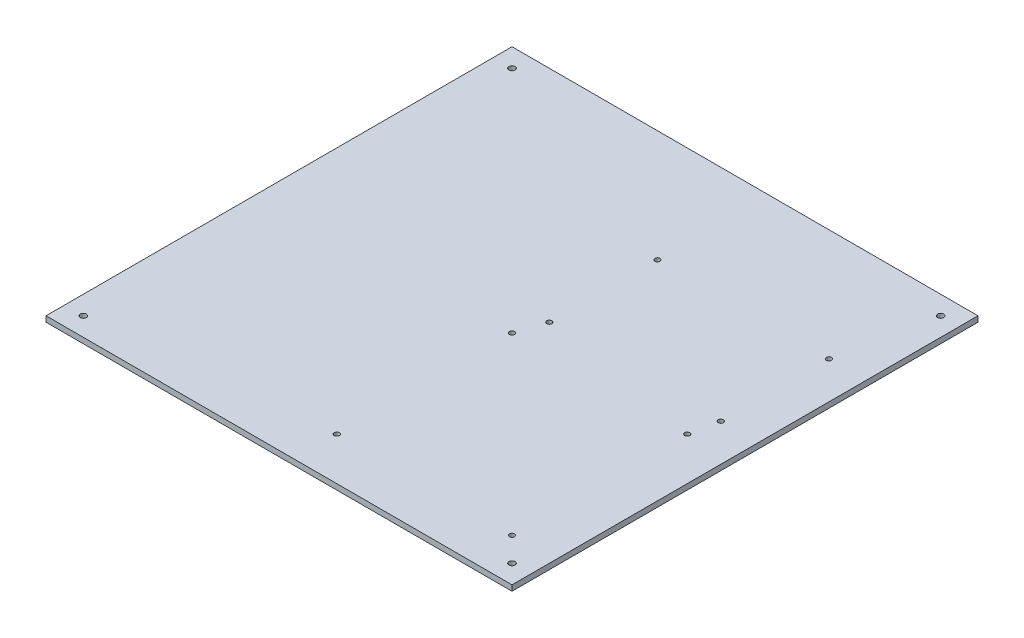
SolidWorks part; units mm, degrees
ref_plane "Front Plane" through (0, 0, 0) normal (0, 0, 1) x (1, 0, 0)
ref_plane "Top Plane" through (0, 0, 0) normal (0, 1, 0) x (1, 0, 0)
ref_plane "Right Plane" through (0, 0, 0) normal (1, 0, 0) x (0, 0, -1)
sketch "Sketch1" plane through (0, 0, 0) normal (0, 1, 0) x (1, 0, 0)
  line L0 (0, 0) -> (0, -250) construction
  line L1 (-125, 0) -> (125, 0)
  line L2 (-125, 0) -> (-125, -250)
  line L3 (-125, -250) -> (125, -250)
  line L4 (125, 0) -> (125, -250)
  line L5 (0, -1.65) -> (0, 1.65) construction
  line L6 (-125, -125) -> (125, -125) construction
  line L7 (55, -130) -> (55, -230) construction
  line L8 (-105, -161.34) -> (-31.34, -161.34) construction
  line L9 (-105, -15) -> (-31.34, -15) construction
  line L10 (-105, -15) -> (-105, -88.66) construction
  line L11 (-105, -88.66) -> (-31.34, -88.66) construction
  line L12 (-31.34, -15) -> (-31.34, -88.66) construction
  line L13 (-105, -161.34) -> (-105, -235) construction
  line L14 (-105, -235) -> (-31.34, -235) construction
  line L15 (-31.34, -161.34) -> (-31.34, -235) construction
  line L16 (-105, -88.66) -> (-105, -161.34) construction
  line L17 (5, -130) -> (105, -130) construction
  line L18 (5, -130) -> (5, -230) construction
  line L19 (5, -230) -> (105, -230) construction
  line L20 (105, -130) -> (105, -230) construction
  line L21 (5, -180) -> (105, -180) construction
  line L22 (-60.805, -122.8687) -> (-38.005, -122.8687) construction
  line L23 (9, -43) -> (109, -43) construction
  line L24 (9, -43) -> (9, -122) construction
  line L25 (9, -122) -> (109, -122) construction
  line L26 (109, -43) -> (109, -122) construction
  line L27 (-102.037, -122.1462) -> (-79.237, -122.1462) construction
  line L28 (-102.037, -122.1462) -> (-102.037, -145.0462) construction
  line L29 (-102.037, -145.0462) -> (-79.237, -145.0462) construction
  line L30 (-79.237, -122.1462) -> (-79.237, -145.0462) construction
  line L35 (-60.805, -122.8687) -> (-60.805, -145.7687) construction
  line L36 (-60.805, -145.7687) -> (-38.005, -145.7687) construction
  line L37 (-38.005, -122.8687) -> (-38.005, -145.7687) construction
  circle A3 centre (-115, -240) radius 1.65
  circle A4 centre (115, -240) radius 1.65
  circle A5 centre (-115, -10) radius 1.65
  circle A6 centre (115, -10) radius 1.65
  circle A7 centre (13, -60) radius 1.375
  circle A8 centre (13, -118) radius 1.375
  circle A9 centre (105, -118) radius 1.375
  circle A10 centre (105, -60) radius 1.375
  circle A11 centre (8, -133) radius 1.375
  circle A12 centre (102, -133) radius 1.375
  circle A13 centre (102, -227) radius 1.375
  circle A14 centre (8, -227) radius 1.375
  dimension "D1" = 3.3
  dimension "D2" = 10
  dimension "D12" = 2.75
  dimension "D20" = 2.75
  dimension "D3" = 10
  dimension "D4" = 250
  dimension "D5" = 250
  dimension "D6" = 73.66
  dimension "D7" = 15
  dimension "D8" = 20
  dimension "D9" = 58
  dimension "D10" = 92
  dimension "D11" = 58
  dimension "D13" = 20
  dimension "D14" = 60
  dimension "D15" = 100
  dimension "D16" = 100
  dimension "D17" = 20
  dimension "D18" = 20
  dimension "D19" = 3
  dimension "D21" = 3
  dimension "D22" = 17
  dimension "D23" = 79
  dimension "D24" = 100
  dimension "D25" = 4
  dimension "D26" = 22.9
  dimension "D27" = 22.8
extrude "Boss-Extrude1" add sketch "Sketch1" along normal blind 3
equation "\"cf_tube_outer_diameter\" = 25mm"
equation "\"cf_tube_inner_diameter\" = 21mm"
equation "\"mid_plate_mid_to_top\" = 100mm"
equation "\"mid_plate_mid_to_bottom\" = 30mm"
equation "\"mid_plate_horizontal_spacing\" = 250mm"
equation "\"cf_plate_thickness\" = 4mm"
equation "\"mid_tube_length\" = 500mm"
equation "\"mid_plate_bottom_width\"= 150mm"
equation "\"mid_support_plate_distance\" = 250mm"
equation "\"nut_strip_2_hole_distance\" = 7mm"
equation "\"nut_strip_hole_diameter\" = 2.5mm"
equation "\"nut_strip_hole_to_edge_distance\" = 2.5mm"
